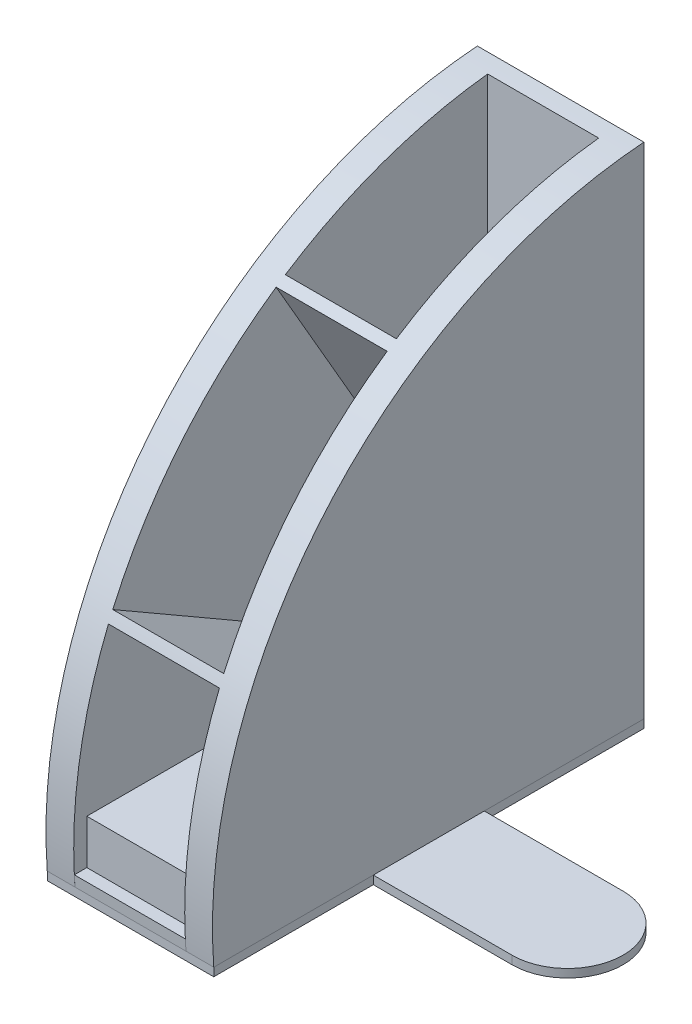
SolidWorks part; units mm, degrees
note: The reader was unsure of these and kept them because the rebuilt part matched: shared geometry of "Sketch1<2>", "Sketch5<4>".
ref_plane "Front Plane" through (0, 0, 0) normal (0, 0, 1) x (1, 0, 0)
ref_plane "Top Plane" through (0, 0, 0) normal (0, 1, 0) x (1, 0, 0)
ref_plane "Right Plane" through (0, 0, 0) normal (1, 0, 0) x (0, 0, -1)
sketch "Sketch1" plane through (0, 0, 0) normal (1, 0, 0) x (0, 0, -1)
  line L0 (0, 0) -> (-155, 0)
  line L1 (0, 0) -> (0, 180)
  arc A0 (-155, 0) -> (0, 180) centre (12.5, 12.5) cw
  dimension "D3" = 167.9658
  dimension "D1" = 180
  dimension "D2" = 155
extrude "Boss-Extrude1" add sketch "Sketch1" along normal blind 10
sketch "Sketch2" plane through (10, 0, 0) normal (1, 0, 0) x (0, 0, -1)
  line L0 (-150.7418, 20) -> (-150.7418, 0)
  line L1 (-155, 0) -> (0, 0) construction
  line L2 (-150.7418, 20) -> (0, 20)
  line L3 (0, 0) -> (0, 180) construction
  line L4 (0, 20) -> (0, 0)
  line L5 (0, 0) -> (-150.7418, 0)
  dimension "D1" = 150.7418
  dimension "D2" = 20
extrude "Boss-Extrude2" add sketch "Sketch2" along normal blind 40
extrude "Boss-Extrude3" add sketch "Sketch1<2>" along normal blind 10 from surface at 50 starting at face at (50, 10, 75.3709)
sketch "Sketch1<2>" plane through (0, 0, 0) normal (1, 0, 0) x (0, 0, -1) same geometry as "Sketch1"
sketch "Sketch3" plane through (10, 0, 0) normal (1, 0, 0) x (0, 0, -1)
  line L0 (-155, 0) -> (-155.2483, 3.9564)
  line L1 (-155.2483, 3.9564) -> (-150.7418, 3.9564)
  line L2 (-150.7418, 20) -> (-150.7418, 0) construction
  line L3 (-150.7418, 3.9564) -> (-150.7418, 0)
  line L4 (-150.7418, 0) -> (-155, 0)
  arc A0 (0, 180) -> (-155, 0) centre (12.5, 12.5) ccw construction
  dimension "D1" = 4.5065
extrude "Boss-Extrude4" add sketch "Sketch3" along normal up to next
sketch "Sketch4" plane through (50, 0, 0) normal (-1, 0, 0) x (0, 0, 1)
  line L0 (6.285, 179.412) -> (6.285, 20)
  line L1 (0, 20) -> (150.7418, 20) construction
  line L2 (6.285, 20) -> (0, 20)
  line L3 (0, 20) -> (0, 180)
  arc A0 (155.2483, 3.9564) -> (0, 180) centre (-12.5, 12.5) ccw construction
  arc A1 (6.285, 179.412) -> (0, 180) centre (-12.5, 12.5) ccw
  point P7 (0, 0)
  dimension "D1" = 159.412
extrude "Boss-Extrude5" add sketch "Sketch4" along normal up to next
sketch "Sketch5" plane through (10, 0, 0) normal (1, 0, 0) x (0, 0, -1)
  line L0 (-155, 0) -> (0, 0) construction
  line L1 (0, 0) -> (0, 180) construction
  line L2 (0, 0) -> (0, 180)
  line L3 (-155, 0) -> (0, 0)
  line L4 (-15.9957, 35.7666) -> (-82.5263, 151.0009)
  line L5 (-31.6214, 16.4431) -> (-141.3865, 79.816)
  line L6 (-142.9574, 76.1042) -> (-32.7917, 12.5)
  line L7 (-79.194, 153.2292) -> (-12.4861, 37.6876)
  arc A0 (-33.6233, 0) -> (0, 41.2006) centre (3.7887, 3.7887) cw
  arc A1 (0, 180) -> (-155, 0) centre (12.5, 12.5) ccw construction
  arc A2 (-79.194, 153.2292) -> (-82.5263, 151.0009) centre (12.5, 12.5) ccw
  arc A3 (-141.3865, 79.816) -> (-142.9574, 76.1042) centre (12.5, 12.5) ccw
  dimension "D1" = 30
  dimension "D3" = 4
  dimension "D2" = 30
  dimension "D4" = 4
  dimension "D5" = 126.7458
  dimension "D6" = 133.4159
extrude "Boss-Extrude8" add sketch "Sketch5" along normal up to surface (40 mm away) contours L2 L6 L0 L5 | L4 A0 L7 L2 up to face at (50, 51.3699, 100.8155)
extrude "Boss-Extrude9" add sketch "Sketch5<4>" along normal up to surface (40 mm away) contours A0 L3 L2 L4 L0 | A0 L0 L4 up to face at (50, 85.6682, 48.5607)
sketch "Sketch5<4>" plane through (10, 0, 0) normal (1, 0, 0) x (0, 0, -1) same geometry as "Sketch5"
sketch "Sketch6" plane through (0, 0, 0) normal (0, -1, 0) x (1, 0, 0)
  line L0 (60, 155) -> (60, 0) construction
  line L1 (60, 97.5) -> (60, 57.5)
  line L2 (60, 97.5) -> (110, 97.5)
  line L3 (60, 57.5) -> (110, 57.5)
  line L10 (0, 155) -> (0, 0)
  line L11 (0, 0) -> (60, 0)
  line L12 (60, 0) -> (60, 155)
  line L13 (60, 155) -> (50, 155)
  line L14 (50, 155) -> (10, 155)
  line L15 (10, 155) -> (0, 155)
  line L16 (0, 155) -> (0, 0)
  line L17 (0, 0) -> (60, 0)
  line L18 (60, 0) -> (60, 155)
  line L19 (60, 155) -> (50, 155)
  line L20 (50, 155) -> (10, 155)
  line L21 (10, 155) -> (0, 155)
  arc A0 (110, 97.5) -> (110, 57.5) centre (110, 77.5) cw
  line M4 (0, 155) -> (0, 0)
  line M5 (0, 0) -> (60, 0)
  line M6 (60, 0) -> (60, 155)
  line M7 (60, 155) -> (50, 155)
  line M8 (50, 155) -> (10, 155)
  line M9 (10, 155) -> (0, 155)
  dimension "D1" = 40
  dimension "D2" = 50
  dimension "D3" = 50
  dimension "D4" = 57.5
  dimension "D5" = 0
extrude "Boss-Extrude10" add sketch "Sketch6" along normal blind 3 separate body contours A0 L2 L3 M6 | M9 M4 M5 M6 M7 M8
